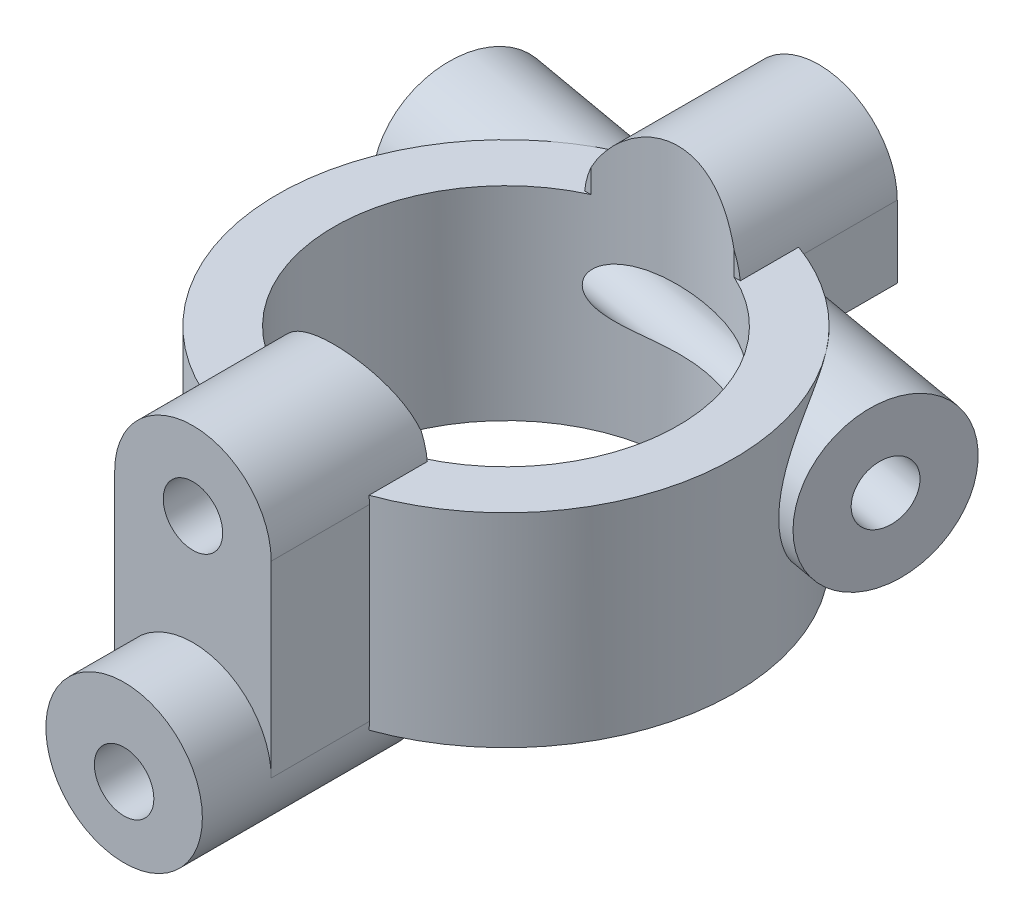
SolidWorks part; units mm, degrees
ref_plane "Front Plane" through (0, 0, 0) normal (0, 0, 1) x (1, 0, 0)
ref_plane "Top Plane" through (0, 0, 0) normal (0, 1, 0) x (1, 0, 0)
ref_plane "Right Plane" through (0, 0, 0) normal (1, 0, 0) x (0, 0, -1)
sketch "Sketch1" plane through (0, 0, 0) normal (0, 1, 0) x (1, 0, 0)
  circle A0 centre (0, 0) radius 9.271
  dimension "D2" = 18.542
extrude "Boss-Extrude1" add sketch "Sketch1" along normal blind 8.255
ref_plane "Plane1" through (0, 0, 6.35) normal (0, 0, 1) x (1, 0, 0)
ref_plane "Plane2" through (0, 0, -6.35) normal (0, 0, 1) x (1, 0, 0)
sketch "Sketch2" plane through (0, 0, 6.35) normal (0, 0, 1) x (1, 0, 0)
  line L0 (0, 8.255) -> (0, 0) construction
  line L2 (-6.985, 4.1275) -> (6.985, 4.1275) construction
  line L3 (9.271, 8.255) -> (-9.271, 8.255) construction
  line L5 (0, -2.8575) -> (0, 11.1125) construction
  line L7 (3.175, 0.3175) -> (3.175, 7.9375)
  line L9 (-3.175, 0.3175) -> (-3.175, 7.9375)
  line L10 (3.175, 0.3175) -> (-3.175, 7.9375) construction
  line L11 (3.175, 7.9375) -> (-3.175, 0.3175) construction
  arc A0 (-3.175, 7.9375) -> (3.175, 7.9375) centre (0, 7.9375) cw
  arc A1 (-3.175, 0.3175) -> (3.175, 0.3175) centre (0, 0.3175) ccw
  point P7 (-24.4635, -4.5524)
  point P8 (-24.2339, 2.0689)
  point P11 (0, 4.1275)
  dimension "D2" = 13.97
  dimension "D4" = 6.985
  dimension "D5" = 3.175
  dimension "D6" = 3.175
  dimension "D1" = 6.35
  dimension "D3" = 3.175
extrude "Boss-Extrude2" add sketch "Sketch2" along normal blind 6.35
sketch "Sketch7" plane through (0, 0, -6.35) normal (0, 0, 1) x (1, 0, 0)
  line L0 (-9.271, 0) -> (9.271, 0) construction
  line L2 (3.175, 7.9248) -> (3.175, 5.0038)
  line L3 (-3.175, 7.9248) -> (-3.175, 5.0038)
  line L4 (3.175, 5.0038) -> (1.2443, 5.0038)
  line L5 (-1.2443, 5.0038) -> (-3.175, 5.0038)
  arc A0 (3.175, 7.9248) -> (-3.175, 7.9248) centre (0, 7.9248) ccw
  arc A1 (1.2443, 5.0038) -> (-1.2443, 5.0038) centre (0, 7.9248) cw
  dimension "D3" = 3.175
  dimension "D4" = 3.175
  dimension "D1" = 7.9248
  dimension "D2" = 6.35
  dimension "D6" = 5.0038
  dimension "D7" = 1.9147
extrude "Boss-Extrude4" add sketch "Sketch7" against normal blind 6.35
sketch "Sketch4" plane through (0, 0, 12.7) normal (0, 0, 1) x (1, 0, 0)
  circle A0 centre (0, 0.3175) radius 3.175
  arc A1 (-3.175, 0.3175) -> (3.175, 0.3175) centre (0, 0.3175) ccw construction
  dimension "D1" = 6.35
extrude "Boss-Extrude3" add sketch "Sketch4" along normal blind 2.794
sketch "Sketch5" plane through (0, 0, 12.7) normal (0, 0, 1) x (1, 0, 0)
  circle A0 centre (0, 7.9375) radius 1.2065
  dimension "D1" = 2.413
sketch "Sketch6" plane through (0, 0, 15.494) normal (0, 0, 1) x (1, 0, 0)
  circle A0 centre (0, 0) radius 1.2065
  dimension "D1" = 2.413
ref_plane "Plane3" through (-9.1302, 0, -1.6099) normal (-0.9848, 0, -0.1736) x (-0.1736, 0, 0.9848)
sketch "Sketch9" plane through (-9.1302, 0, -1.6099) normal (-0.9848, 0, -0.1736) x (-0.1736, 0, 0.9848)
  line L1 (9.1323, 8.255) -> (-8.0359, 8.255) construction
  circle A0 centre (-6.8033, 5.0122) radius 3.2428
  dimension "D1" = 6.4855
  dimension "D2" = 5.1524
extrude "Boss-Extrude5" add sketch "Sketch9" against normal blind 18.542 and the other way blind 2.5019
sketch "Sketch11" plane through (0, 8.255, 0) normal (0, 1, 0) x (1, 0, 0)
  circle A0 centre (0, 0) radius 6.985
  dimension "D1" = 13.97
extrude "Cut-Extrude9" cut sketch "Sketch11" against normal blind 19.304 and the other way blind 19.304
extrude "Cut-Extrude10" cut sketch "Sketch6" against normal up to next
sketch "Sketch12" plane through (-11.594, 0, -2.0443) normal (-0.9848, 0, -0.1736) x (-0.1736, 0, 0.9848)
  circle A0 centre (-6.8033, 5.0122) radius 1.2065
  dimension "D1" = 2.413
extrude "Cut-Extrude11" cut sketch "Sketch12" against normal through all
extrude "Cut-Extrude12" cut sketch "Sketch5" against normal blind 3.81
mirror "Mirror2" about plane through (0, 0, 0) normal (0, 0, 1) of "Cut-Extrude12"
